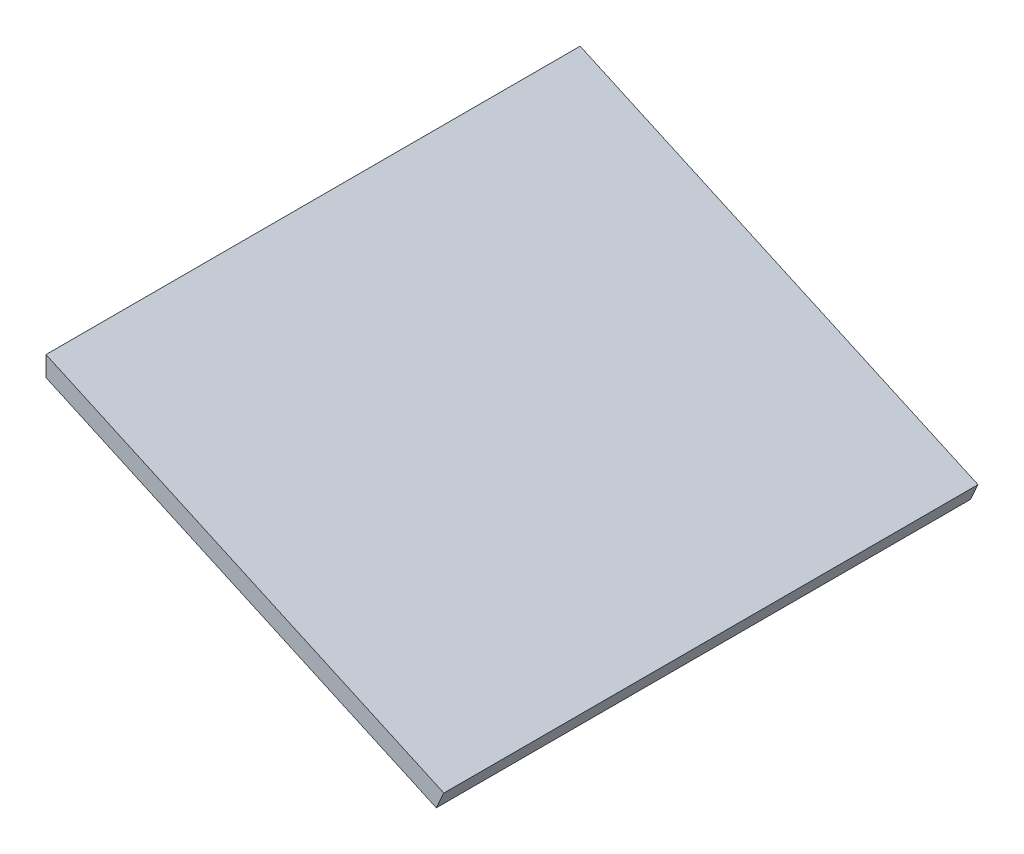
SolidWorks part; units mm, degrees
ref_plane "Front Plane" through (0, 0, 0) normal (0, 0, 1) x (1, 0, 0)
ref_plane "Top Plane" through (0, 0, 0) normal (0, 1, 0) x (1, 0, 0)
ref_plane "Right Plane" through (0, 0, 0) normal (1, 0, 0) x (0, 0, -1)
sketch "Sketch3" plane through (0, 0, 0) normal (0, 0, 1) x (1, 0, 0)
  line L0 (-108.5345, -3.9032) -> (-108.5345, 1464.0363)
  line L1 (-108.5345, -3.9032) -> (-870.5345, -3.9032)
  line L2 (-870.5345, -3.9032) -> (-870.5345, 625.8363)
  line L3 (-972.1345, 737.9573) -> (-972.1345, 834.2968)
  line L4 (-768.9345, 834.2968) -> (-768.9345, 986.6968)
  line L5 (-972.1345, 834.2968) -> (-768.9345, 834.2968)
  line L6 (-528.0858, 1843.9468) -> (-737.1845, 1843.9468)
  line L7 (-968.4148, 728.977) -> (-874.2542, 634.8165)
  line L8 (-737.1845, 1672.0154) -> (-737.1845, 1762.6932)
  line L9 (-520.195, 1875.6968) -> (-756.2345, 1875.6968)
  line L10 (-112.2542, 1473.0165) -> (-511.2148, 1871.977)
  line L11 (-737.1845, 1692.941) -> (-241.631, 1467.6894)
  line L12 (-596.8655, 1608.234) -> (-737.1845, 983.1768)
  line L13 (-763.9746, 985.3593) -> (-203.7845, 834.2968)
  line L14 (-761.4898, 1669.1128) -> (-638.6318, 1613.2683)
  line L15 (-631.4955, 1598.9249) -> (-768.9345, 986.6968)
  line L16 (-768.9345, 1680.6745) -> (-768.9345, 1862.9968)
  line L17 (-737.1845, 1780.4468) -> (-737.1845, 1843.9468)
  line L18 (-737.1845, 1692.941) -> (-737.1845, 1843.9468) construction
  line L19 (-737.1845, 1692.941) -> (-737.1845, 1762.6932) construction
  line L20 (-838.7845, -3.9032) -> (-838.7845, 834.2968)
  line L21 (-745.0674, 1675.5986) -> (-249.5139, 1450.347) construction
  line L22 (-140.2845, -3.9032) -> (-140.2845, 1456.1455)
  line L23 (-140.2845, 1456.1455) -> (-528.0858, 1843.9468)
  line L24 (-537.8111, 1581.3911) -> (-673.6845, 976.1369)
  line L25 (-768.9345, 966.9663) -> (-203.7845, 814.5663)
  line L26 (-737.1845, 1672.0154) -> (-203.7845, 1429.5608)
  line L27 (-528.0858, 1843.9468) -> (-554.3883, 1780.4468)
  line L28 (-140.2845, 1456.1455) -> (-203.7845, 1429.8429)
  line L29 (-775.2845, -3.9032) -> (-775.2845, 834.2968)
  line L30 (-773.8944, 968.3038) -> (-208.7444, 815.9038) construction
  line L31 (-203.7845, -3.9032) -> (-203.7845, 1429.8429)
  line L32 (-203.7845, 1429.8429) -> (-554.3883, 1780.4468)
  line L33 (-554.3883, 1780.4468) -> (-737.1845, 1780.4468)
  line L34 (-768.9345, 966.9663) -> (-763.9746, 985.3593)
  line L35 (-737.1845, 1762.6932) -> (-369.5099, 1595.5683)
  line L36 (-673.6845, 1733.8295) -> (-599.2171, 1699.9807) construction
  line L37 (-737.1845, 1692.941) -> (-625.4936, 1642.1724) construction
  line L38 (-538.5586, 1578.0615) -> (-673.6845, 976.1369) construction
  line L39 (-600.5166, 1591.9704) -> (-737.1845, 983.1768) construction
  line L40 (-554.3883, 1780.4468) -> (-673.6845, 1780.4468) construction
  line L41 (-203.7845, 91.3468) -> (-203.7845, 1429.8429) construction
  line L42 (-140.2845, 27.8468) -> (-140.2845, 1456.1455) construction
  line L43 (-775.2845, 91.3468) -> (-775.2845, 625.8363) construction
  line L44 (-838.7845, 27.8468) -> (-838.7845, 625.8363) construction
  line L45 (-203.7845, 91.3468) -> (-775.2845, 91.3468) construction
  line L46 (-140.2845, 27.8468) -> (-838.7845, 27.8468) construction
  line L47 (-940.3845, 745.8481) -> (-851.8036, 657.2672) construction
  line L48 (-843.7807, 739.0468) -> (-806.9023, 702.1685) construction
  line L49 (-843.7807, 739.0468) -> (-673.6845, 739.0468) construction
  line L50 (-940.3845, 802.5468) -> (-737.1845, 802.5468) construction
  line L51 (-940.3845, 745.8481) -> (-940.3845, 802.5468) construction
  line L52 (-843.7807, 739.0468) -> (-843.7807, 739.0468) construction
  line L53 (-673.6845, 1733.8295) -> (-673.6845, 1780.4468) construction
  line L54 (-756.2345, 1692.941) -> (-756.2345, 1792.2779) construction
  line L55 (-756.2345, 1792.2779) -> (-361.627, 1612.9108) construction
  line L56 (-673.6845, 739.0468) -> (-673.6845, 976.1369) construction
  line L57 (-737.1845, 802.5468) -> (-737.1845, 983.1768) construction
  line L58 (-768.9345, 986.6968) -> (-203.7845, 834.2968) construction
  line L59 (-203.7845, 834.2968) -> (-208.7444, 815.9038)
  line L60 (-768.9345, 901.198) -> (-203.7845, 748.798)
  line L61 (-846.7775, 922.1894) -> (-163.9675, 738.0608) construction
  line L62 (-768.9345, 966.9663) -> (-208.7444, 815.9038) construction
  line L64 (-808.7515, 1063.2022) -> (-125.9415, 879.0737) construction
  line L65 (-125.9415, 879.0737) -> (-163.9675, 738.0608) construction
  line L66 (-846.7775, 922.1894) -> (-808.7515, 1063.2022) construction
  arc A0 (-108.5345, 1464.0363) -> (-112.2542, 1473.0165) centre (-121.2345, 1464.0363) ccw
  arc A1 (-511.2148, 1871.977) -> (-520.195, 1875.6968) centre (-520.195, 1862.9968) ccw
  arc A2 (-768.9345, 1862.9968) -> (-756.2345, 1875.6968) centre (-756.2345, 1862.9968) cw
  arc A3 (-768.9345, 1680.6745) -> (-761.4898, 1669.1128) centre (-756.2345, 1680.6745) ccw
  arc A4 (-631.4955, 1598.9249) -> (-638.6318, 1613.2683) centre (-643.8871, 1601.7067) ccw
  arc A5 (-972.1345, 737.9573) -> (-968.4148, 728.977) centre (-959.4345, 737.9573) ccw
  arc A6 (-870.5345, 625.8363) -> (-874.2542, 634.8165) centre (-883.2345, 625.8363) ccw
  arc A7 (-737.1845, 1843.9468) -> (-737.1845, 1843.9468) centre (-737.1845, 1843.9468) cw
  arc A8 (-737.1845, 1692.941) -> (-737.1845, 1692.941) centre (-737.1845, 1692.941) ccw
  arc A12 (-140.2845, 1456.1455) -> (-140.2845, 1456.1455) centre (-140.2845, 1456.1455) ccw
  arc A13 (-528.0858, 1843.9468) -> (-528.0858, 1843.9468) centre (-528.0858, 1843.9468) ccw
  arc A14 (-600.5166, 1591.9704) -> (-625.4936, 1642.1724) centre (-643.8871, 1601.7067) ccw construction
  arc A16 (-203.7845, 1429.8429) -> (-203.7845, 1429.8429) centre (-203.7845, 1429.8429) ccw
  arc A17 (-554.3883, 1780.4468) -> (-554.3883, 1780.4468) centre (-554.3883, 1780.4468) ccw
  arc A18 (-673.6845, 1780.4468) -> (-673.6845, 1780.4468) centre (-673.6845, 1780.4468) cw
  arc A19 (-673.6845, 1733.8295) -> (-673.6845, 1733.8295) centre (-673.6845, 1733.8295) ccw
  arc A20 (-838.7845, 625.8363) -> (-851.8036, 657.2672) centre (-883.2345, 625.8363) ccw construction
  arc A21 (-775.2845, 625.8363) -> (-806.9023, 702.1685) centre (-883.2345, 625.8363) ccw construction
  arc A22 (-843.7807, 739.0468) -> (-843.7807, 739.0468) centre (-843.7807, 739.0468) ccw construction
  arc A23 (-940.3845, 745.8481) -> (-940.3845, 745.8481) centre (-940.3845, 745.8481) ccw construction
  arc A24 (-756.2345, 1692.941) -> (-745.0674, 1675.5986) centre (-737.1845, 1692.941) ccw construction
  dimension "D1" = 12.7
  dimension "D2" = 31.75
  dimension "D3" = 63.5
  dimension "D4" = 19.05
  dimension "D5" = 19.05
  dimension "D6" = 63.5
sketch "Sketch6" plane through (0, 0, 0) normal (0, 0, 1) x (1, 0, 0)
  line L0 (-737.1845, 1672.0154) -> (-737.1845, 1692.941)
  line L1 (-737.1845, 1692.941) -> (-320.9649, 1503.7503)
  line L2 (-737.1845, 1672.0154) -> (-328.8479, 1486.4078)
  line L5 (-320.9649, 1503.7503) -> (-328.8479, 1486.4078)
extrude "Boss-Extrude1" add sketch "Sketch6" along normal blind 558.8
